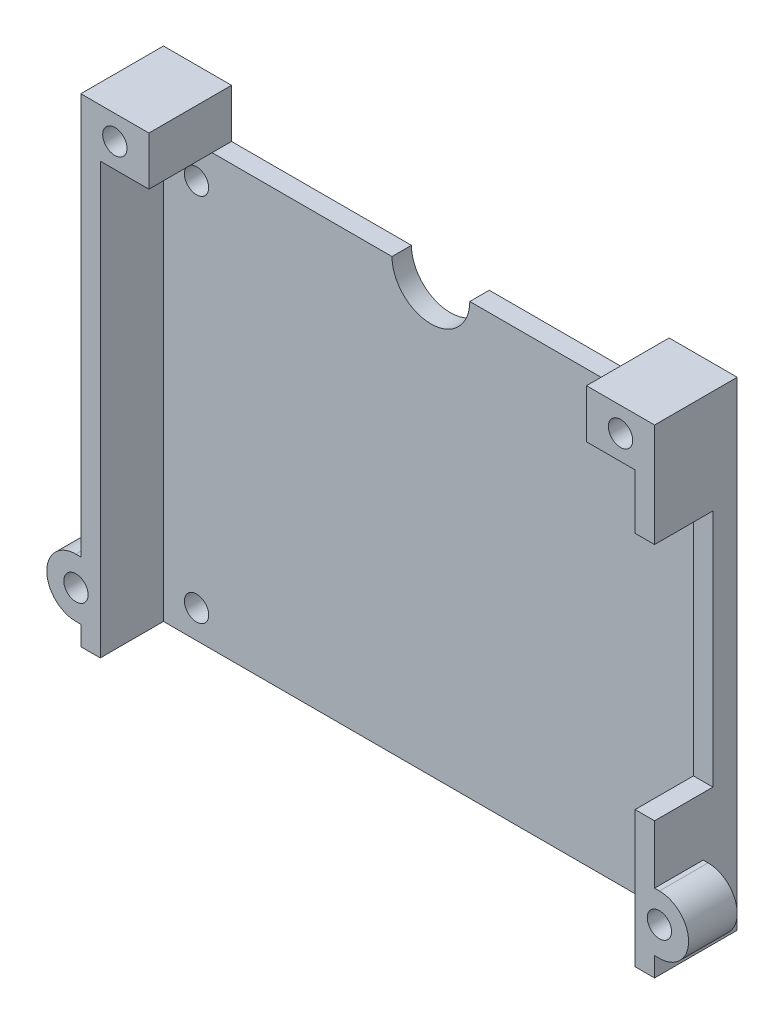
SolidWorks part; units mm, degrees
ref_plane "Front Plane" through (0, 0, 0) normal (0, 0, 1) x (1, 0, 0)
ref_plane "Top Plane" through (0, 0, 0) normal (0, 1, 0) x (1, 0, 0)
ref_plane "Right Plane" through (0, 0, 0) normal (1, 0, 0) x (0, 0, -1)
sketch "Sketch1" plane through (0, 0, 0) normal (0, 1, 0) x (1, 0, 0)
  line L0 (0, 0) -> (2, 0)
  line L1 (0, 0) -> (59, 0) construction
  line L2 (0, 0) -> (0, 8.5)
  line L3 (0, 8.5) -> (59, 8.5)
  line L4 (59, 0) -> (59, 8.5)
  line L5 (2, 0) -> (2, 6.5)
  line L6 (2, 6.5) -> (57, 6.5)
  line L7 (57, 6.5) -> (57, 0)
  line L8 (57, 0) -> (59, 0)
  dimension "D1" = 59
  dimension "D2" = 8.5
  dimension "D3" = 2
  dimension "D4" = 6.5
  dimension "D5" = 55
extrude "Boss-Extrude1" add sketch "Sketch1" along normal blind 44.25
sketch "Sketch2" plane through (59, 0, 0) normal (1, 0, 0) x (0, 0, -1)
  line L0 (0, 0) -> (0, 14) construction
  line L1 (0, 44.25) -> (0, 0) construction
  line L2 (0, 14) -> (6, 14)
  line L3 (6, 14) -> (6, 38.6)
  line L4 (6, 38.6) -> (0, 38.6)
  line L5 (0, 38.6) -> (0, 14)
  dimension "D1" = 14
  dimension "D2" = 6
  dimension "D3" = 24.6
extrude "Cut-Extrude1" cut sketch "Sketch2" against normal blind 10
sketch "Sketch3" plane through (0, 0, -8.5) normal (0, 0, -1) x (-1, 0, 0)
  line L0 (-59, 0) -> (-59, 8) construction
  line L1 (-59, 44.25) -> (-59, 0) construction
  line L2 (-59, 8) -> (-59, 2)
  line L3 (-59, 5) -> (-59.5, 5) construction
  line L4 (-59, 8) -> (-59.5, 8)
  line L5 (-59, 2) -> (-59.5, 2)
  line L6 (0, 0) -> (0, 8) construction
  line L7 (0, 44.25) -> (0, 0) construction
  line L8 (0, 8) -> (0.5, 8)
  line L9 (0, 8) -> (0, 2)
  line L10 (0, 2) -> (0.5, 2)
  line L11 (0, 5) -> (0.5, 5) construction
  arc A0 (-59.5, 8) -> (-59.5, 2) centre (-59.5, 5) ccw
  circle A1 centre (-59.5, 5) radius 1.25
  arc A2 (0.5, 8) -> (0.5, 2) centre (0.5, 5) cw
  circle A3 centre (0.5, 5) radius 1.25
  line M5 (0, 0) -> (0, 44.25)
  line M7 (-59, 44.25) -> (-59, 0)
  dimension "D4" = 3
  dimension "D5" = 2.5
  dimension "D11" = 3
  dimension "D12" = 2.5
  dimension "D1" = 8
  dimension "D2" = 6
  dimension "D3" = 0.5
  dimension "D6" = 8
  dimension "D7" = 0.5
  dimension "D8" = 6
  dimension "D9" = 0.5
extrude "Boss-Extrude2" add sketch "Sketch3" against normal blind 8.5 contours A1 L4 A0 L5 M7 | A3 L10 A2 L8 M5 region at (59.0695, 7.0728, -8.5) region at (-0.25, 7.9305, -8.5)
extrude "Cut-Extrude2" cut sketch "Sketch3<3>" against normal blind 11 contours L2 A1 | L9 A3 region at (58.6906, 5, -8.5) region at (0.3094, 5, -8.5)
sketch "Sketch3<3>" plane through (0, 0, -8.5) normal (0, 0, -1) x (-1, 0, 0) same geometry as "Sketch3"
sketch "Sketch4" plane through (0, 44.25, 0) normal (0, 1, 0) x (1, 0, 0)
  line L0 (59, 8.5) -> (0, 8.5) construction
  line L1 (0, 0) -> (7, 0)
  line L2 (0, 0) -> (0, 8.5)
  line L3 (0, 8.5) -> (7, 8.5)
  line L4 (7, 0) -> (7, 8.5)
  line L6 (59, 0) -> (52, 0)
  line L7 (59, 0) -> (59, 8.5)
  line L8 (59, 8.5) -> (52, 8.5)
  line L9 (52, 0) -> (52, 8.5)
  dimension "D1" = 7
  dimension "D2" = 7
extrude "Boss-Extrude3" add sketch "Sketch4" along normal blind 5
sketch "Sketch5" plane through (0, 0, -8.5) normal (0, 0, -1) x (-1, 0, 0)
  line L0 (-59, 49.25) -> (-52, 44.25) construction
  line L1 (0, 49.25) -> (-7, 44.25) construction
  circle A0 centre (-55.5, 46.75) radius 1.25
  circle A1 centre (-3.5, 46.75) radius 1.25
  dimension "D1" = 2.5
  dimension "D2" = 2.5
extrude "Cut-Extrude3" cut sketch "Sketch5" against normal through all
sketch "Sketch7" plane through (0, 0, -8.5) normal (0, 0, -1) x (-1, 0, 0)
  line L0 (-59, 0) -> (-59, 2.9) construction
  line L1 (-59, 2) -> (-59, 0) construction
  line L2 (-59, 2.9) -> (0, 2.9) construction
  line L3 (0, 2) -> (0, 0) construction
  line L4 (-53.6, 2.9) -> (-5.4, 2.9)
  line L5 (-53.6, 2.9) -> (-53.6, 40.95) construction
  line L6 (-53.6, 40.95) -> (-5.4, 40.95) construction
  circle A0 centre (-53.6, 2.9) radius 1.25
  circle A1 centre (-5.4, 2.9) radius 1.25
  circle A2 centre (-53.6, 40.95) radius 1.25
  circle A3 centre (-5.4, 40.95) radius 1.25
  point P11 (-29.5, 2.9)
  dimension "D3" = 2.5
  dimension "D4" = 2.5
  dimension "D6" = 2.5
  dimension "D8" = 2.5
  dimension "D1" = 2.9
  dimension "D2" = 48.2
  dimension "D5" = 38.05
  dimension "D7" = 48.2
extrude "Cut-Extrude4" cut sketch "Sketch7" against normal blind 10 contours A2 | A3 | A1 | A0 region at (5.4, 4.1146, -8.5) region at (54.8146, 2.9, -8.5) region at (53.6, 40.95, -8.5) region at (5.4, 40.95, -8.5)
sketch "Sketch8" plane through (0, 0, -8.5) normal (0, 0, -1) x (-1, 0, 0)
  line L0 (-52, 44.25) -> (-7, 44.25) construction
  circle A0 centre (-29.5, 44.25) radius 4
  dimension "D1" = 8
extrude "Cut-Extrude5" cut sketch "Sketch8" against normal through all
extrude "Cut-Extrude6" cut sketch "Sketch3<4>" against normal blind 3.5 contours A1 L4 A0 L5 M7 | A3 L10 A2 L8 M5 region at (59.0695, 7.0728, -8.5) region at (-0.25, 7.9305, -8.5)
sketch "Sketch3<4>" plane through (0, 0, -8.5) normal (0, 0, -1) x (-1, 0, 0) same geometry as "Sketch3"
extrude "Boss-Extrude4" add sketch "Sketch3<5>" against normal blind 3 contours L9 A3 | L2 A1 region at (58.6906, 5, -8.5) region at (0.3094, 5, -8.5)
sketch "Sketch3<5>" plane through (0, 0, -8.5) normal (0, 0, -1) x (-1, 0, 0) same geometry as "Sketch3"
